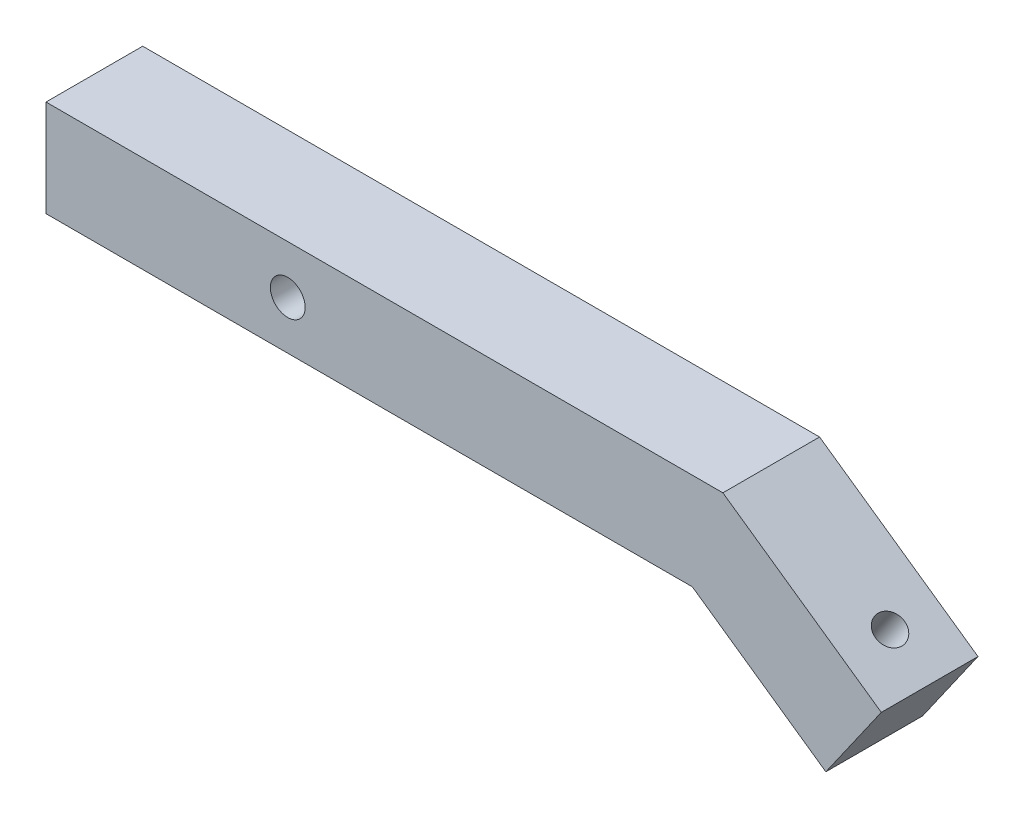
SolidWorks part; units mm, degrees
ref_plane "Front Plane" through (0, 0, 0) normal (0, 0, 1) x (1, 0, 0)
ref_plane "Top Plane" through (0, 0, 0) normal (0, 1, 0) x (1, 0, 0)
ref_plane "Right Plane" through (0, 0, 0) normal (1, 0, 0) x (0, 0, -1)
sketch "Sketch1" plane through (0, 0, 0) normal (0, 0, 1) x (1, 0, 0)
  line L0 (0, 0) -> (88.9, 0)
  line L1 (88.9, 0) -> (109.7065, -14.5688)
  line L2 (109.7065, -14.5688) -> (102.422, -24.9721)
  line L3 (102.422, -24.9721) -> (84.8957, -12.7)
  line L4 (84.8957, -12.7) -> (0, -12.7)
  line L5 (0, -12.7) -> (0, 0)
  dimension "D1" = 12.7
  dimension "D2" = 12.7
  dimension "D3" = 145
  dimension "D4" = 88.9
  dimension "D5" = 25.4
extrude "Boss-Extrude1" add sketch "Sketch1" along normal blind 12.7
sketch "Sketch2" plane through (0, 0, 0) normal (0, 0, -1) x (-1, 0, 0)
  line L0 (0, 0) -> (0, -12.7) construction
  line L1 (0, -12.7) -> (-84.8957, -12.7) construction
  circle A0 centre (-31.75, -6.35) radius 2.286
  dimension "D1" = 4.572
  dimension "D3" = 6.35
  dimension "D2" = 31.75
extrude "Cut-Extrude1" cut sketch "Sketch2" against normal blind 12.7
sketch "Sketch3" plane through (21.9628, 31.3661, 0) normal (-0.5736, -0.8192, 0) x (0.8192, -0.5736, 0)
  line L0 (76.8269, 0) -> (98.2226, 0) construction
  line L1 (98.2226, 12.7) -> (98.2226, 0) construction
  circle A0 centre (91.8726, 6.35) radius 1.905
  dimension "D3" = 3.81
  dimension "D1" = 6.35
  dimension "D2" = 6.35
extrude "Cut-Extrude2" cut sketch "Sketch3" against normal blind 12.7
